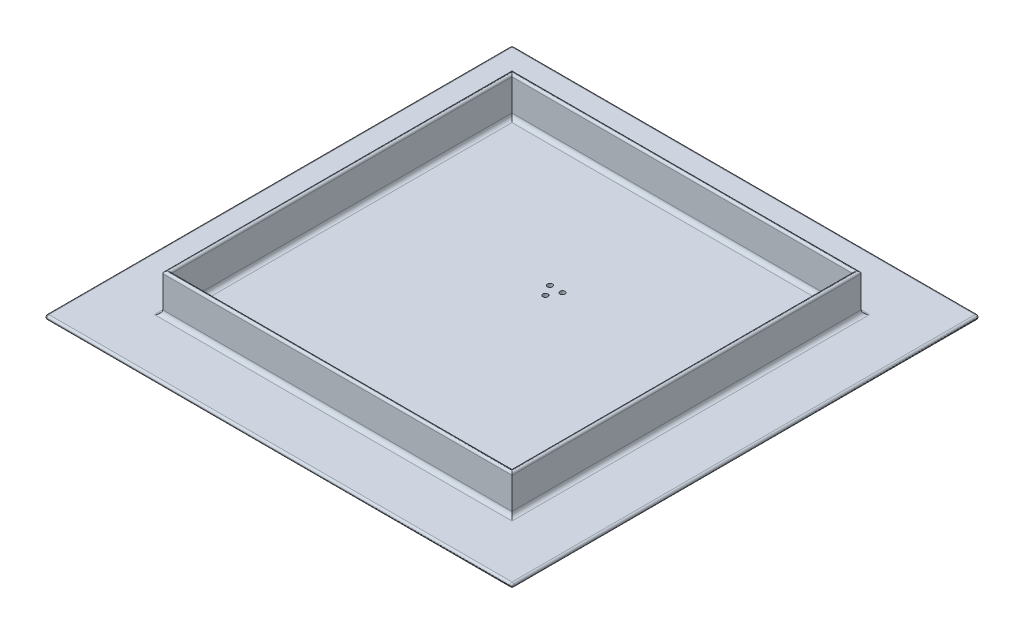
SolidWorks part; units mm, degrees
ref_plane "Front Plane" through (0, 0, 0) normal (0, 0, 1) x (1, 0, 0)
ref_plane "Top Plane" through (0, 0, 0) normal (0, 1, 0) x (1, 0, 0)
ref_plane "Right Plane" through (0, 0, 0) normal (1, 0, 0) x (0, 0, -1)
sketch "Sketch1" plane through (0, 0, 0) normal (0, 1, 0) x (1, 0, 0)
  line L1 (-280, 280) -> (280, 280)
  line L2 (-280, 280) -> (-280, -280)
  line L3 (-280, -280) -> (280, -280)
  line L4 (280, 280) -> (280, -280)
  line L5 (-280, 280) -> (280, -280) construction
  line L6 (-280, -280) -> (280, 280) construction
  point P0 (0, 0)
  dimension "D1" = 560
  dimension "D2" = 560
extrude "Boss-Extrude1" add sketch "Sketch1" along normal blind 5
sketch "Sketch2" plane through (0, 5, 0) normal (0, 1, 0) x (1, 0, 0)
  line L1 (-280, 280) -> (280, 280)
  line L2 (-280, 280) -> (-280, -280)
  line L3 (-280, -280) -> (280, -280)
  line L4 (280, 280) -> (280, -280)
  line L5 (-280, 280) -> (280, -280) construction
  line L6 (-280, -280) -> (280, 280) construction
  line L7 (-209.2893, 209.2893) -> (209.2893, 209.2893)
  line L8 (-209.2893, 209.2893) -> (-209.2893, -209.2893)
  line L9 (-209.2893, -209.2893) -> (209.2893, -209.2893)
  line L10 (209.2893, 209.2893) -> (209.2893, -209.2893)
  line L11 (-209.2893, 209.2893) -> (209.2893, -209.2893) construction
  line L12 (-209.2893, -209.2893) -> (209.2893, 209.2893) construction
  line L13 (-204.2893, 204.2893) -> (204.2893, 204.2893)
  line L14 (-204.2893, 204.2893) -> (-204.2893, -204.2893)
  line L15 (-204.2893, -204.2893) -> (204.2893, -204.2893)
  line L16 (204.2893, 204.2893) -> (204.2893, -204.2893)
  line L17 (-204.2893, 204.2893) -> (204.2893, -204.2893) construction
  line L18 (-204.2893, -204.2893) -> (204.2893, 204.2893) construction
  point P0 (0, 0)
  point P7 (0, 0)
  point P12 (0, 0)
  dimension "D1" = 100
  dimension "D2" = 5
  dimension "D3" = 5
  dimension "D4" = 5
  dimension "D5" = 5
extrude "Boss-Extrude2" add sketch "Sketch2" along normal blind 45 contours L10 L7 L8 L9 L13 L16 L15 L14 region at (0, 5, -208.6974)
sketch "Sketch3" plane through (0, 5, 0) normal (0, 1, 0) x (1, 0, 0)
  line L1 (0, 40) -> (7.5, 52.9904) construction
  line L2 (7.5, 52.9904) -> (-7.5, 52.9904) construction
  line L3 (-7.5, 52.9904) -> (0, 40) construction
  circle A0 centre (0, 48.6603) radius 4.3301 construction
  circle A1 centre (7.5, 52.9904) radius 3
  circle A2 centre (0, 40) radius 3
  circle A3 centre (-7.5, 52.9904) radius 3
  dimension "D3" = 6
  dimension "D1" = 40
  dimension "D2" = 15
extrude "Cut-Extrude1" cut sketch "Sketch3" against normal blind 5
fillet "Fillet1" radius 5 8 edges at (-209.2893, 5, 0) (0, 5, 209.2893) (209.2893, 5, 0) (0, 5, -209.2893) (-204.2893, 5, 0) (0, 5, 204.2893) (204.2893, 5, 0) (0, 5, -204.2893)
fillet "Fillet2" radius 2.5 8 edges at (-204.2893, 50, 0) (0, 50, 204.2893) (204.2893, 50, 0) (0, 50, -204.2893) (0, 50, 209.2893) (-209.2893, 50, 0) (0, 50, -209.2893) (209.2893, 50, 0)
fillet "Fillet3" radius 2.5 8 edges at (0, 5, -280) (0, 0, -280) (280, 5, 0) (280, 0, 0) (-280, 5, 0) (-280, 0, 0) (0, 5, 280) (0, 0, 280)
